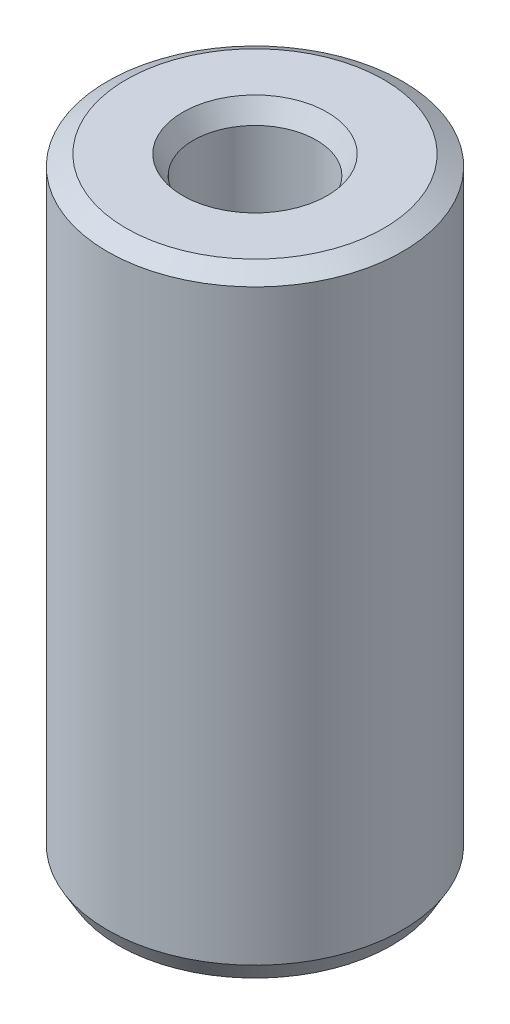
SolidWorks part; units mm, degrees
ref_plane "Front Plane" through (0, 0, 0) normal (0, 0, 1) x (1, 0, 0)
ref_plane "Top Plane" through (0, 0, 0) normal (0, 1, 0) x (1, 0, 0)
ref_plane "Right Plane" through (0, 0, 0) normal (1, 0, 0) x (0, 0, -1)
sketch "Sketch1" plane through (0, 0, 0) normal (0, 1, 0) x (1, 0, 0)
  circle A0 centre (0, 0) radius 35
  dimension "SLEEVE_OD" = 70
extrude "Boss-Extrude1" add sketch "Sketch1" along normal blind 146.3534
sketch "Sketch2" plane through (0, 0, 0) normal (0, 1, 0) x (1, 0, 0)
  circle A0 centre (0, 0) radius 14.5794
  dimension "BORE_D" = 29.1587
extrude "Cut-Extrude1" cut sketch "Sketch2" along normal through all
chamfer "Chamfer1" distance 2.5693 angle 60 4 edges at (0, 146.3534, 14.5794) (0, 0, 14.5794) (0, 0, 35) (0, 146.3534, 35) first distance on face at (0, 146.3534, 14.5794) first distance on face at (0, 0, 14.5794) first distance on face at (0, 146.3534, 35)
